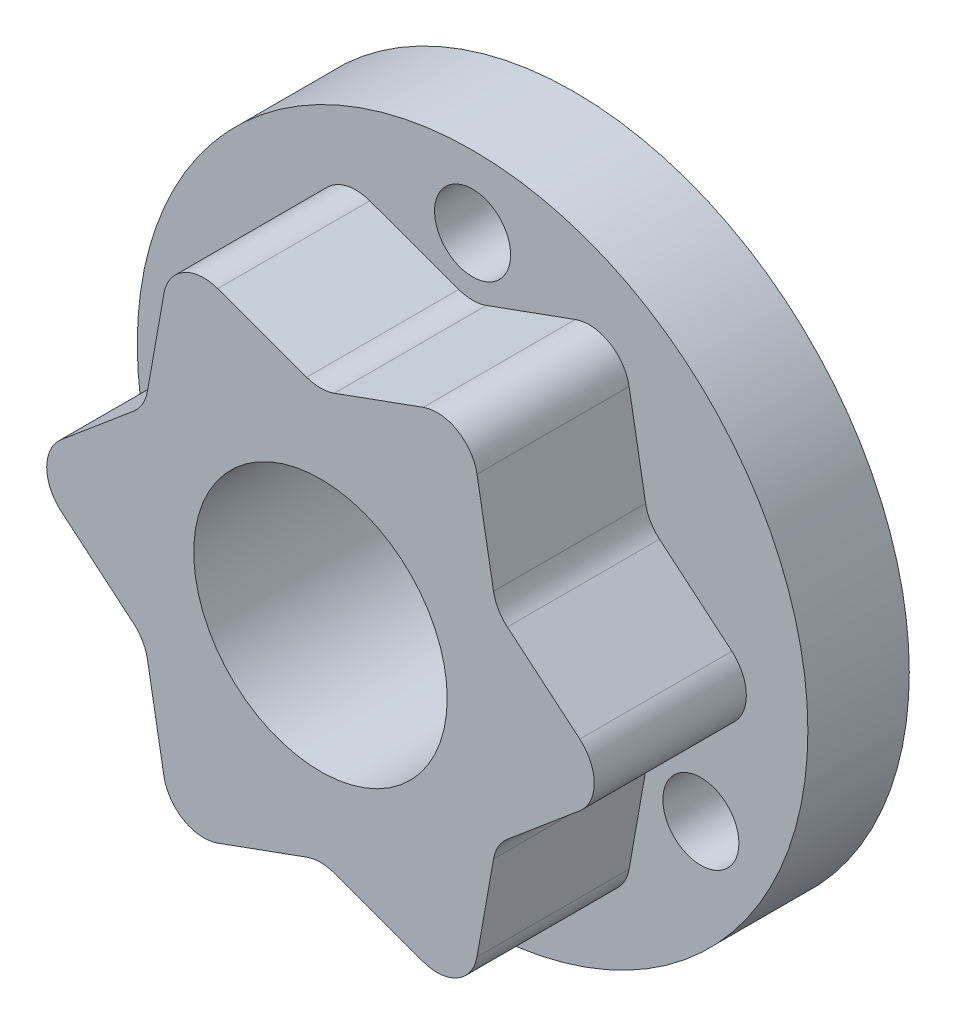
SolidWorks part; units mm, degrees
ref_plane "Front Plane" through (0, 0, 0) normal (0, 0, 1) x (1, 0, 0)
ref_plane "Top Plane" through (0, 0, 0) normal (0, 1, 0) x (1, 0, 0)
ref_plane "Right Plane" through (0, 0, 0) normal (1, 0, 0) x (0, 0, -1)
sketch "Sketch1" plane through (0, 0, 0) normal (0, 0, 1) x (1, 0, 0)
  line L0 (0, 0) -> (0, 21) construction
  circle A0 centre (0, 0) radius 21
  circle A1 centre (0, 0) radius 7.9375
  circle A2 centre (0, 16.51) radius 2.3813
  circle A3 centre (14.2981, -8.255) radius 2.3813
  circle A4 centre (-14.2981, -8.255) radius 2.3813
  point P14 (0, 0)
  dimension "D1" = 42
  dimension "D2" = 15.875
  dimension "D3" = 4.7625
  dimension "D4" = 16.51
  dimension "D5" = 3
extrude "Boss-Extrude1" add sketch "Sketch1" along normal blind 6.35
sketch "Sketch3" plane through (0, 0, 6.35) normal (0, 0, 1) x (1, 0, 0)
  line L0 (0, 0) -> (0, 21) construction
  line L1 (0, 0) -> (18.1865, 10.5) construction
  line L2 (0, 0) -> (18.5523, 32.1335) construction
  line L3 (0.8666, 13.0145) -> (6.4359, 15.0359)
  line L4 (9.8035, 13.0916) -> (10.8376, 7.2577)
  line L5 (16.2394, -1.9443) -> (11.7042, -5.7568)
  line L6 (11.7042, 5.7568) -> (16.2394, 1.9443)
  line L7 (6.4359, -15.0359) -> (0.8666, -13.0145)
  line L8 (10.8376, -7.2577) -> (9.8035, -13.0916)
  line L9 (-9.8035, -13.0916) -> (-10.8376, -7.2577)
  line L10 (-0.8666, -13.0145) -> (-6.4359, -15.0359)
  line L11 (-16.2394, 1.9443) -> (-11.7042, 5.7568)
  line L12 (-11.7042, -5.7568) -> (-16.2394, -1.9443)
  line L13 (-6.4359, 15.0359) -> (-0.8666, 13.0145)
  line L14 (-10.8376, 7.2577) -> (-9.8035, 13.0916)
  circle A0 centre (0, 0) radius 7.9375 construction
  circle A1 centre (0, 0) radius 7.9375
  circle A3 centre (0, 0) radius 21 construction
  arc A4 (6.4359, 15.0359) -> (9.8035, 13.0916) centre (7.3025, 12.6483) cw
  arc A5 (16.2394, 1.9443) -> (16.2394, -1.9443) centre (14.605, 0) cw
  arc A6 (9.8035, -13.0916) -> (6.4359, -15.0359) centre (7.3025, -12.6483) cw
  arc A7 (-6.4359, -15.0359) -> (-9.8035, -13.0916) centre (-7.3025, -12.6483) cw
  arc A8 (-16.2394, -1.9443) -> (-16.2394, 1.9443) centre (-14.605, 0) cw
  arc A9 (-9.8035, 13.0916) -> (-6.4359, 15.0359) centre (-7.3025, 12.6483) cw
  arc A10 (0.8666, 13.0145) -> (-0.8666, 13.0145) centre (0, 15.4021) cw
  arc A11 (11.7042, 5.7568) -> (10.8376, 7.2577) centre (13.3386, 7.7011) cw
  arc A12 (10.8376, -7.2577) -> (11.7042, -5.7568) centre (13.3386, -7.7011) cw
  arc A13 (-0.8666, -13.0145) -> (0.8666, -13.0145) centre (0, -15.4021) cw
  arc A14 (-11.7042, -5.7568) -> (-10.8376, -7.2577) centre (-13.3386, -7.7011) cw
  arc A15 (-10.8376, 7.2577) -> (-11.7042, 5.7568) centre (-13.3386, 7.7011) cw
  point P14 (6.5382, 10.0937)
  point P16 (9.2761, 16.0668)
  point P20 (0, 12.7)
  point P45 (0, 0)
  point P59 (0, 0)
  dimension "D4" = 2.54
  dimension "D7" = 2.54
  dimension "D2" = 60
  dimension "D3" = 30
  dimension "D5" = 6
  dimension "D8" = 6
extrude "Boss-Extrude2" add sketch "Sketch3" along normal blind 9.525
sketch "Sketch5" plane through (0, 0, 15.875) normal (0, 0, 1) x (1, 0, 0)
  line L12 (6.4359, 15.0359) -> (0.8666, 13.0145)
  line L13 (-0.8666, 13.0145) -> (-6.4359, 15.0359)
  line L14 (-9.8035, 13.0916) -> (-10.8376, 7.2577)
  line L15 (-11.7042, 5.7568) -> (-16.2394, 1.9443)
  line L16 (-16.2394, -1.9443) -> (-11.7042, -5.7568)
  line L17 (-10.8376, -7.2577) -> (-9.8035, -13.0916)
  line L18 (-6.4359, -15.0359) -> (-0.8666, -13.0145)
  line L19 (0.8666, -13.0145) -> (6.4359, -15.0359)
  line L20 (9.8035, -13.0916) -> (10.8376, -7.2577)
  line L21 (11.7042, -5.7568) -> (16.2394, -1.9443)
  line L22 (16.2394, 1.9443) -> (11.7042, 5.7568)
  line L23 (10.8376, 7.2577) -> (9.8035, 13.0916)
  line L24 (6.4359, 15.0359) -> (0.8666, 13.0145)
  line L25 (-0.8666, 13.0145) -> (-6.4359, 15.0359)
  line L26 (-9.8035, 13.0916) -> (-10.8376, 7.2577)
  line L27 (-11.7042, 5.7568) -> (-16.2394, 1.9443)
  line L28 (-16.2394, -1.9443) -> (-11.7042, -5.7568)
  line L29 (-10.8376, -7.2577) -> (-9.8035, -13.0916)
  line L30 (-6.4359, -15.0359) -> (-0.8666, -13.0145)
  line L31 (0.8666, -13.0145) -> (6.4359, -15.0359)
  line L32 (9.8035, -13.0916) -> (10.8376, -7.2577)
  line L33 (11.7042, -5.7568) -> (16.2394, -1.9443)
  line L34 (16.2394, 1.9443) -> (11.7042, 5.7568)
  line L35 (10.8376, 7.2577) -> (9.8035, 13.0916)
  circle A0 centre (-14.2981, -8.255) radius 2.3813 construction
  circle A1 centre (0, 16.51) radius 2.3813 construction
  circle A2 centre (14.2981, -8.255) radius 2.3813 construction
  circle A3 centre (-14.2981, -8.255) radius 2.3813
  circle A4 centre (0, 16.51) radius 2.3813
  circle A5 centre (14.2981, -8.255) radius 2.3813
  arc A12 (9.8035, 13.0916) -> (6.4359, 15.0359) centre (7.3025, 12.6483) ccw
  arc A13 (-0.8666, 13.0145) -> (0.8666, 13.0145) centre (0, 15.4021) ccw
  arc A14 (-6.4359, 15.0359) -> (-9.8035, 13.0916) centre (-7.3025, 12.6483) ccw
  arc A15 (-11.7042, 5.7568) -> (-10.8376, 7.2577) centre (-13.3386, 7.7011) ccw
  arc A16 (-16.2394, 1.9443) -> (-16.2394, -1.9443) centre (-14.605, 0) ccw
  arc A17 (-10.8376, -7.2577) -> (-11.7042, -5.7568) centre (-13.3386, -7.7011) ccw
  arc A18 (-9.8035, -13.0916) -> (-6.4359, -15.0359) centre (-7.3025, -12.6483) ccw
  arc A19 (0.8666, -13.0145) -> (-0.8666, -13.0145) centre (0, -15.4021) ccw
  arc A20 (6.4359, -15.0359) -> (9.8035, -13.0916) centre (7.3025, -12.6483) ccw
  arc A21 (11.7042, -5.7568) -> (10.8376, -7.2577) centre (13.3386, -7.7011) ccw
  arc A22 (16.2394, -1.9443) -> (16.2394, 1.9443) centre (14.605, 0) ccw
  arc A23 (10.8376, 7.2577) -> (11.7042, 5.7568) centre (13.3386, 7.7011) ccw
  arc A24 (9.8035, 13.0916) -> (6.4359, 15.0359) centre (7.3025, 12.6483) ccw
  arc A25 (-0.8666, 13.0145) -> (0.8666, 13.0145) centre (0, 15.4021) ccw
  arc A26 (-6.4359, 15.0359) -> (-9.8035, 13.0916) centre (-7.3025, 12.6483) ccw
  arc A27 (-11.7042, 5.7568) -> (-10.8376, 7.2577) centre (-13.3386, 7.7011) ccw
  arc A28 (-16.2394, 1.9443) -> (-16.2394, -1.9443) centre (-14.605, 0) ccw
  arc A29 (-10.8376, -7.2577) -> (-11.7042, -5.7568) centre (-13.3386, -7.7011) ccw
  arc A30 (-9.8035, -13.0916) -> (-6.4359, -15.0359) centre (-7.3025, -12.6483) ccw
  arc A31 (0.8666, -13.0145) -> (-0.8666, -13.0145) centre (0, -15.4021) ccw
  arc A32 (6.4359, -15.0359) -> (9.8035, -13.0916) centre (7.3025, -12.6483) ccw
  arc A33 (11.7042, -5.7568) -> (10.8376, -7.2577) centre (13.3386, -7.7011) ccw
  arc A34 (16.2394, -1.9443) -> (16.2394, 1.9443) centre (14.605, 0) ccw
  arc A35 (10.8376, 7.2577) -> (11.7042, 5.7568) centre (13.3386, 7.7011) ccw
  dimension "D1" = 0
